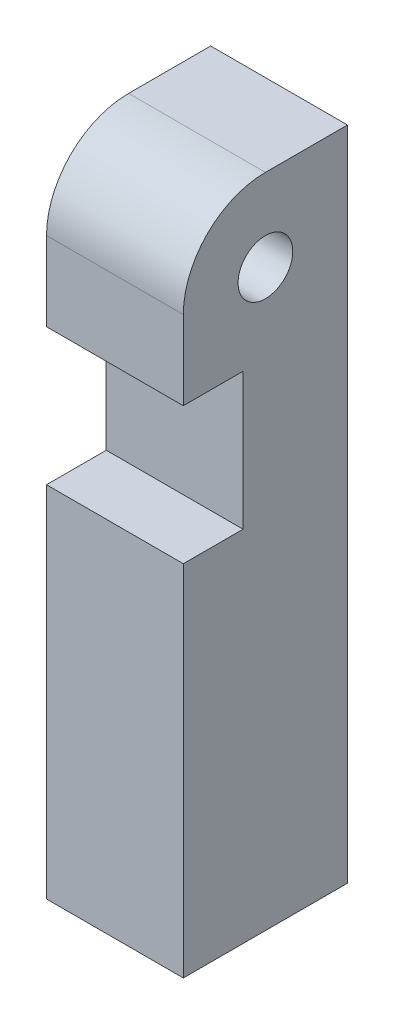
SolidWorks part; units mm, degrees
ref_plane "Front Plane" through (0, 0, 0) normal (0, 0, 1) x (1, 0, 0)
ref_plane "Top Plane" through (0, 0, 0) normal (0, 1, 0) x (1, 0, 0)
ref_plane "Right Plane" through (0, 0, 0) normal (1, 0, 0) x (0, 0, -1)
sketch "Elevator Paddle" plane through (0, 0, 0) normal (1, 0, 0) x (0, 0, -1)
  line L0 (3.81, 3.81) -> (3.81, -26.67)
  line L1 (3.81, -26.67) -> (-3.81, -26.67)
  line L2 (-3.81, -26.67) -> (-3.81, -10.016)
  line L3 (-6.4983, 38.1) -> (3.6147, 38.1)
  line L4 (3.81, 3.81) -> (0, 3.81)
  line L5 (-3.81, -3.666) -> (-1.0375, -3.666)
  line L6 (-1.0375, -3.666) -> (-1.0375, -10.016)
  line L7 (-1.0375, -10.016) -> (-3.81, -10.016)
  line L8 (-3.81, -3.666) -> (-3.81, 0)
  line L9 (1.735, 3.81) -> (1.735, -26.67) construction
  line L10 (-3.81, -12.8389) -> (1.735, -12.8389) construction
  line L11 (-1.0375, -10.016) -> (-1.0375, -12.8389) construction
  circle A0 centre (0, 0) radius 1.27
  arc A1 (0, 3.81) -> (-3.81, 0) centre (0, 0) ccw
  point P17 (-1.0375, -12.8389)
  dimension "D3" = 2.54
  dimension "D1" = 2.54
  dimension "D2" = 2.54
  dimension "D4" = 25.4
  dimension "D6" = 2.7725
  dimension "D7" = 2.54
  dimension "D5" = 6.35
  dimension "D8" = 2.075
extrude "Boss-Extrude1" add sketch "Elevator Paddle" along normal blind 6.35 contours L0 L1 L3 A0 region at (0, -12.3189, -0.2513)
equation "\"Ball Diameter\"= 1.75in"
equation "\"Sheet Thickness\"= 0.25in"
equation "\"Screw Diameter\"= .17in"
equation "\"Robot Diameter\"= 14in"
equation "\"Castor Screw Diameter\"= 0.22in"
equation "\"Wheel Diameter\" = 4in"
equation "\"Nut Diameter\" = 8.4mm"
equation "\"Nut Height\" = 2.9mm"
equation "\"Screw Height\" = 0.55in"
equation "\"D1@Boss-Extrude1\"=\"Sheet Thickness\""
equation "\"Pulley Diameter\" = 1in"
equation "\"Reactor Height\" = 14in"
equation "\"Elevator Height\" = 11.5in"
equation "\"Elevator Width\" = \"Ball Diameter\" + 0.25in"
equation "\"Elevator Bearing Diameter\" = sqr(2*(\"Sheet Thickness\"^2)) + 0.2in"
equation "\"Elevator Axle Endcap Diameter\" = \"Pulley Diameter\" + 0.25in"
equation "\"Elevator Axle Length\" = \"Elevator Width\" + 8*\"Sheet Thickness\""
equation "\"Elevator Clearance from Axis\" = (\"Pulley Diameter\"/2) + \"Ball Diameter\" + 0.5in"
equation "\"D5@Elevator Paddle\"=\"Sheet Thickness\""
equation "\"D6@Elevator Paddle\"=\"Sheet Thickness\"/2"
equation "\"D8@Elevator Paddle\"=(\"Elevator Axle Endcap Diameter\"-\"Pulley Diameter\")/2 - 1.1mm"
